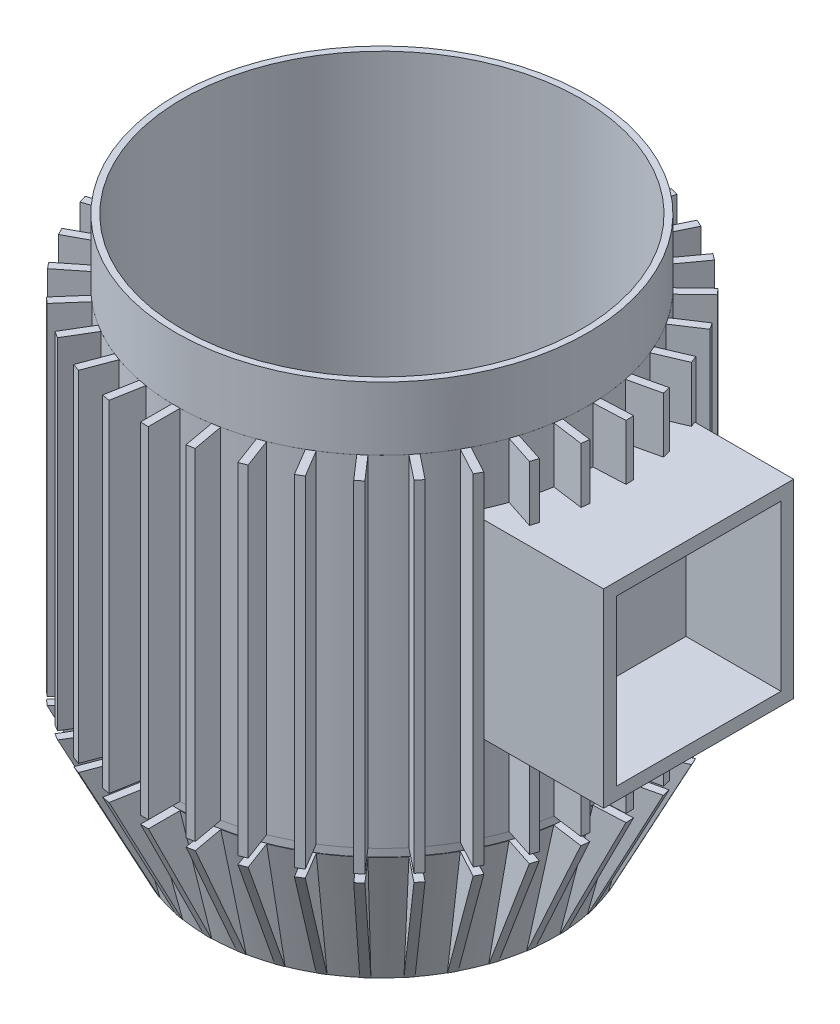
SolidWorks part; units mm, degrees
ref_plane "Front Plane" through (0, 0, 0) normal (0, 0, 1) x (1, 0, 0)
ref_plane "Top Plane" through (0, 0, 0) normal (0, 1, 0) x (1, 0, 0)
ref_plane "Right Plane" through (0, 0, 0) normal (1, 0, 0) x (0, 0, -1)
sketch "Sketch1" plane through (0, 0, 0) normal (0, 1, 0) x (1, 0, 0)
  circle A0 centre (0, 0) radius 1651
  dimension "D1" = 3302
extrude "Boss-Extrude1" add sketch "Sketch1" against normal blind 4318
chamfer "Chamfer1" distance 254 distance2 1016 1 edges at (0, -4318, 1651) first distance on face at (0, -4318, 1651)
shell "Shell1" thickness 50.8 removed face at (0, 0, 1651)
ref_plane "Plane4" through (0, 0, 1905) normal (0, 0, 1) x (1, 0, 0)
sketch "Sketch2" plane through (0, 0, 1905) normal (0, 0, 1) x (1, 0, 0)
  line L0 (1651, 0) -> (-1651, 0) construction
  line L1 (-31.75, 0) -> (31.75, 0)
  line L2 (-31.75, 0) -> (-31.75, -4318)
  line L3 (-31.75, -4318) -> (31.75, -4318)
  line L4 (31.75, 0) -> (31.75, -4318)
  line L5 (-1397, -4318) -> (1397, -4318) construction
  line L6 (0, 0) -> (0, -4565.7037) construction
  dimension "D1" = 63.5
extrude "Boss-Extrude2" add sketch "Sketch2" against normal up to next
pattern_circular "CirPattern1" count 35 over 360 about axis through (0, -4318, 0) along (0, 1, 0) of "Boss-Extrude2" reverse direction yes
sketch "Sketch3" plane through (0, 0, 0) normal (0, 0, 1) x (1, 0, 0)
  line L0 (-1398.8655, -4318) -> (-1904.5063, -3302)
  line L1 (-1904.5063, -4318) -> (-1904.5063, 0) construction
  line L2 (-1398.8655, -4318) -> (-2052.1864, -4573.4164)
  line L3 (-2052.1864, -4573.4164) -> (-2052.1864, -3238.5)
  line L4 (-2052.1864, -3238.5) -> (-1647.6081, -3238.5)
  line L7 (-1647.6081, -3302) -> (-1904.5063, -3302)
  line L8 (-1647.6081, -3238.5) -> (-1647.6081, -3302)
  line L9 (0, 0) -> (0, -4960.7075) construction
  dimension "D1" = 63.5
revolve "Cut-Revolve1" cut sketch "Sketch3" angle 360 about L9
sketch "Sketch4" plane through (0, -4318, 0) normal (0, -1, 0) x (1, 0, 0)
  circle A0 centre (0, 0) radius 254
  dimension "D1" = 508
extrude "Cut-Extrude1" cut sketch "Sketch4" against normal through all
ref_plane "Plane5" through (2540, 0, 0) normal (1, 0, 0) x (0, 0, -1)
sketch "Sketch6" plane through (2540, 0, 0) normal (1, 0, 0) x (0, 0, -1)
  line L0 (3763.1942, -2443.5551) -> (-1009.808, -1761.5916) construction
  line L1 (762, -2476.5) -> (-762, -2476.5)
  line L2 (762, -2476.5) -> (762, -952.5)
  line L3 (762, -952.5) -> (-762, -952.5)
  line L4 (-762, -2476.5) -> (-762, -952.5)
  line L5 (0, 0) -> (0, -4799.0579) construction
  line L7 (-1647.6081, -3238.5) -> (1647.6081, -3238.5) construction
  dimension "D1" = 1524
  dimension "D2" = 1524
  dimension "D3" = 762
extrude "Boss-Extrude3" add sketch "Sketch6" against normal up to next
sketch "Sketch7" plane through (2540, 0, 0) normal (1, 0, 0) x (0, 0, -1)
  line L0 (660.4, -1054.1) -> (-660.4, -1054.1)
  line L1 (-660.4, -1054.1) -> (-660.4, -2374.9)
  line L2 (-660.4, -2374.9) -> (660.4, -2374.9)
  line L3 (660.4, -2374.9) -> (660.4, -1054.1)
  line L4 (762, -2476.5) -> (762, -952.5)
  line L5 (762, -952.5) -> (-762, -952.5)
  line L6 (-762, -952.5) -> (-762, -2476.5)
  line L7 (-762, -2476.5) -> (762, -2476.5)
  line L8 (762, -2476.5) -> (762, -952.5)
  line L9 (762, -952.5) -> (-762, -952.5)
  line L10 (-762, -952.5) -> (-762, -2476.5)
  line L11 (-762, -2476.5) -> (762, -2476.5)
  dimension "D1" = 0
  dimension "D2" = 101.6
extrude "Cut-Extrude3" cut sketch "Sketch7" against normal blind 762 contours L0 L1 L2 L3
sketch "Sketch8" plane through (0, 0, 0) normal (1, 0, 0) x (0, 0, -1)
  line L0 (-1650.6947, -3238.5) -> (-1650.6947, 0) construction
  line L1 (-2144.3398, 0) -> (-1650.6947, 0)
  line L2 (-2144.3398, 0) -> (-2144.3398, -508)
  line L3 (-2144.3398, -508) -> (-1650.6947, -508)
  line L4 (-1650.6947, 0) -> (-1650.6947, -508)
  line L5 (-1650.6947, 0) -> (-1905, 0) construction
  line L6 (0, 0) -> (0, -4807.3928) construction
  line L7 (1600.2, 0) -> (-1600.2, 0) construction
  dimension "D1" = 508
revolve "Cut-Revolve2" cut sketch "Sketch8" angle 360 about L6
scale "Scale1" scale about centroid uniform scaling yes scale factor 0.02
